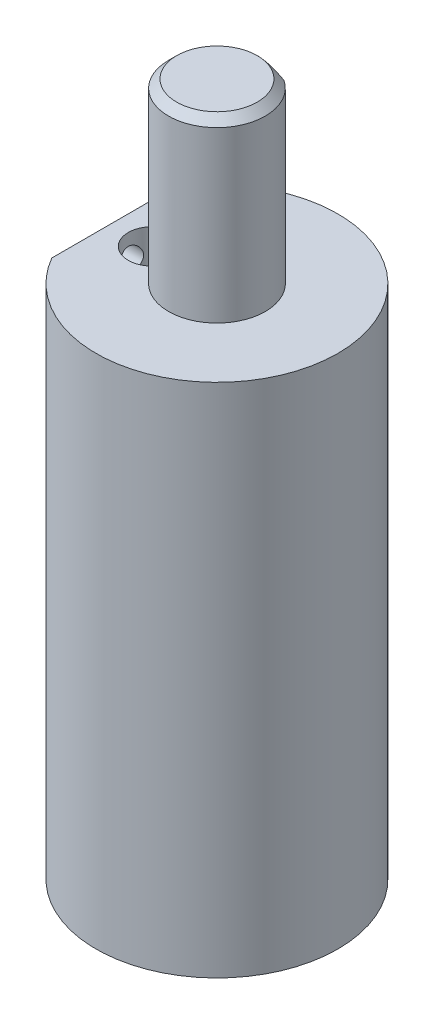
SolidWorks part; units mm, degrees
ref_plane "Front Plane" through (0, 0, 0) normal (0, 0, 1) x (1, 0, 0)
ref_plane "Top Plane" through (0, 0, 0) normal (0, 1, 0) x (1, 0, 0)
ref_plane "Right Plane" through (0, 0, 0) normal (1, 0, 0) x (0, 0, -1)
sketch "Sketch1" plane through (0, 0, 0) normal (0, 1, 0) x (1, 0, 0)
  line L0 (-3.3166, -5) -> (3.3166, -5)
  arc A0 (3.3166, -5) -> (-3.3166, -5) centre (0, 0) ccw
  dimension "D1" = 12
  dimension "D2" = 5
extrude "Boss-Extrude1" add sketch "Sketch1" along normal blind 22
sketch "Sketch2" plane through (0, 0, 0) normal (0, -1, 0) x (1, 0, 0)
  line L0 (-13, 7.4833) -> (-13, -7.4833)
  arc A0 (-13, -7.4833) -> (-13, 7.4833) centre (0, 0) ccw
  dimension "D1" = 30
  dimension "D2" = 13
extrude "Boss-Extrude2" add sketch "Sketch2" along normal blind 64
sketch "Sketch3" plane through (0, -64, 0) normal (0, -1, 0) x (1, 0, 0)
  line L0 (0, 0) -> (-13, 0) construction
  line L1 (-13, 7.4833) -> (-13, -7.4833) construction
  circle A0 centre (-8, 0) radius 3
  dimension "D2" = 6
  dimension "D1" = 8
extrude "Cut-Extrude1" cut sketch "Sketch3" against normal blind 65
sketch "Sketch4" plane through (0, -64, 0) normal (0, -1, 0) x (-1, 0, 0)
  circle A0 centre (-5, 0) radius 6
  dimension "D1" = 5
  dimension "D2" = 12
extrude "Cut-Extrude2" cut sketch "Sketch4" against normal blind 52
sketch "Sketch8" plane through (0, -64, 0) normal (0, -1, 0) x (1, 0, 0)
  line L0 (0, 0) -> (0, 9) construction
  line L1 (0, 0) -> (0, -9) construction
  dimension "D1" = 9
  dimension "D2" = 9
hole_wizard "M4 Tapped Hole2" positions "Sketch18" profile "Sketch19" tap size "M4" standard "ISO"
sketch "Sketch18" plane through (0, -64, 0) normal (0, -1, 0) x (-1, 0, 0)
  point P0 (0, -9)
  point P3 (0, 9)
sketch "Sketch19" plane through (0, -64, 9) normal (1, 0, 0) x (0, 0, -1)
  line L0 (0, 0) -> (0, 17.7914)
  line L1 (0, 17.7914) -> (1.65, 16.8)
  line L2 (1.65, 16.8) -> (1.65, 0.35)
  line L3 (1.65, 0.35) -> (2, 0)
  line L5 (2, 0) -> (0, 0)
  line L6 (-1.65, 0.35) -> (-2, 0) construction
  line L10 (0, 17.7914) -> (-1.65, 16.8) construction
  line L11 (0, -6.35) -> (0, 107.95) construction
  dimension "Tap Drill Dia." = 3.3
  dimension "Tap Drill Depth" = 16.8
  dimension "Near C'Sink Dia." = 4
  dimension "Near C'Sink Angle" = 90
  dimension "Drill Angle" = 118
cosmetic thread "Hole Thread3" parameters "D1"=13.3, "D2"=4
cosmetic thread "Hole Thread4" parameters "D1"=13.3, "D2"=4
sketch "Sketch20" plane through (-13, 0, 0) normal (-1, 0, 0) x (0, 0, 1)
  line L0 (0, -64) -> (0, 1.9118) construction
  line L1 (0, -64) -> (9, -64) construction
  line L2 (0, -64) -> (-9, -64) construction
  circle A0 centre (0, -32) radius 2.5
  circle A1 centre (0, -3) radius 1.5
  dimension "D1" = 3
  dimension "D2" = 5
  dimension "D3" = 32
  dimension "D4" = 61
extrude "Cut-Extrude3" cut sketch "Sketch20" against normal blind 5
sketch "Sketch21" plane through (-13, 0, 0) normal (-1, 0, 0) x (0, 0, 1)
  line L0 (0, 0) -> (0, -64) construction
  line L1 (0, -64) -> (9, -64) construction
  line L2 (0, -64) -> (-9, -64) construction
  circle A0 centre (0, -12) radius 1
  circle A1 centre (0, -54) radius 1
  dimension "D3" = 2
  dimension "D4" = 2
  dimension "D1" = 10
  dimension "D2" = 52
extrude "Cut-Extrude4" cut sketch "Sketch21" against normal blind 15
sketch "Sketch22" plane through (0, 22, 0) normal (0, 1, 0) x (1, 0, 0)
  line L0 (-3.3166, -5) -> (3.3166, -5)
  circle A0 centre (0, 0) radius 6
  line M2 (-3.3166, -5) -> (3.3166, -5)
extrude "Boss-Extrude4" add sketch "Sketch22" against normal blind 22 contours A0 M2 region at (0, 22, 5.403)
sketch "Sketch23" plane through (0, 22, 0) normal (0, 1, 0) x (1, 0, 0)
  line L0 (-3.3166, 5) -> (3.3166, 5)
  circle A1 centre (0, 0) radius 6
  circle M2 centre (0, 0) radius 6
  dimension "D2" = 12
  dimension "D1" = 5
extrude "Cut-Extrude5" cut sketch "Sketch23" against normal blind 22 contours L0 M2 region at (0, 22, -5.403)
chamfer "Chamfer1" distance 1 angle 45 1 edges at (0, 22, 6)
